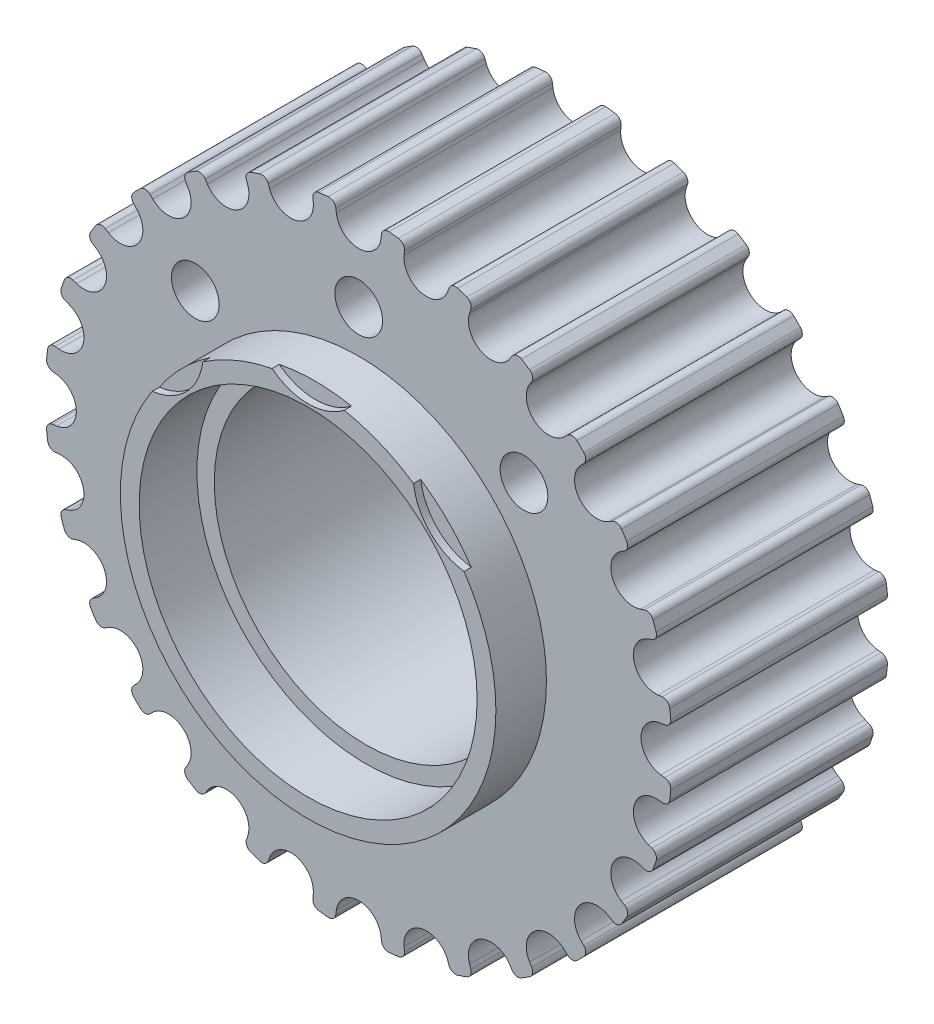
SolidWorks part; units mm, degrees
note: The reader was unsure of these and kept them because the rebuilt part matched: shared geometry of "草图15<2>".
ref_plane "前视基准面" through (0, 0, 0) normal (0, 0, 1) x (1, 0, 0)
ref_plane "上视基准面" through (0, 0, 0) normal (0, 1, 0) x (1, 0, 0)
ref_plane "右视基准面" through (0, 0, 0) normal (1, 0, 0) x (0, 0, -1)
sketch "草图2" plane through (0, 0, 0) normal (0, 0, 1) x (1, 0, 0)
  line L36 (1.3319, 20.7804) -> (1.2989, 20.5118)
  line L37 (-1.7978, 20.5118) -> (-1.8308, 20.7804)
  line L38 (-3.4222, 20.6011) -> (-3.3946, 20.3319)
  line L39 (-6.4137, 19.6428) -> (-6.5056, 19.8973)
  line L40 (-8.0172, 19.3684) -> (-7.9303, 19.1121)
  line L41 (-10.7204, 17.7684) -> (-10.8667, 17.9962)
  line L42 (-12.2227, 17.1441) -> (-12.081, 16.9135)
  line L43 (-14.5021, 14.9827) -> (-14.6954, 15.1722)
  line L44 (-15.8278, 14.0398) -> (-15.6383, 13.8465)
  line L45 (-17.5691, 11.4254) -> (-17.7997, 11.5671)
  line L46 (-18.6517, 10.2111) -> (-18.424, 10.0648)
  line L47 (-19.7676, 7.2748) -> (-20.024, 7.3616)
  line L48 (-20.5529, 5.85) -> (-20.2983, 5.7581)
  line L49 (-20.9874, 2.739) -> (-21.2567, 2.7666)
  line L50 (-21.436, 1.1752) -> (-21.1673, 1.1423)
  line L51 (-21.1673, -1.9545) -> (-21.436, -1.9875)
  line L52 (-21.2567, -3.5789) -> (-20.9874, -3.5512)
  line L53 (-20.2983, -6.5703) -> (-20.5529, -6.6623)
  line L54 (-20.024, -8.1739) -> (-19.7676, -8.087)
  line L55 (-18.424, -10.8771) -> (-18.6517, -11.0234)
  line L56 (-17.7997, -12.3793) -> (-17.5691, -12.2376)
  line L57 (-15.6383, -14.6588) -> (-15.8278, -14.8521)
  line L58 (-14.6954, -15.9845) -> (-14.5021, -15.795)
  line L59 (-12.081, -17.7258) -> (-12.2227, -17.9564)
  line L60 (-10.8667, -18.8084) -> (-10.7204, -18.5807)
  line L61 (-7.9303, -19.9243) -> (-8.0172, -20.1806)
  line L62 (-6.5056, -20.7096) -> (-6.4137, -20.455)
  line L63 (-3.3946, -21.1441) -> (-3.4222, -21.4133)
  line L64 (-1.8308, -21.5926) -> (-1.7978, -21.324)
  line L65 (1.2989, -21.324) -> (1.3319, -21.5926)
  line L66 (2.9233, -21.4133) -> (2.8957, -21.1441)
  line L67 (5.9148, -20.455) -> (6.0067, -20.7096)
  line L68 (7.5183, -20.1806) -> (7.4314, -19.9243)
  line L69 (10.2215, -18.5807) -> (10.3678, -18.8084)
  line L70 (11.7238, -17.9564) -> (11.5821, -17.7258)
  line L71 (14.0032, -15.795) -> (14.1965, -15.9845)
  line L72 (15.3289, -14.8521) -> (15.1394, -14.6588)
  line L73 (17.0702, -12.2376) -> (17.3008, -12.3793)
  line L74 (18.1528, -11.0234) -> (17.9251, -10.8771)
  line L75 (19.2687, -8.087) -> (19.5251, -8.1739)
  line L76 (20.054, -6.6623) -> (19.7994, -6.5703)
  line L77 (20.4885, -3.5512) -> (20.7578, -3.5789)
  line L78 (20.9371, -1.9875) -> (20.6684, -1.9545)
  line L79 (20.6684, 1.1423) -> (20.9371, 1.1752)
  line L80 (20.7578, 2.7666) -> (20.4885, 2.739)
  line L81 (19.7994, 5.7581) -> (20.054, 5.85)
  line L82 (19.5251, 7.3616) -> (19.2687, 7.2748)
  line L83 (17.9251, 10.0648) -> (18.1528, 10.2111)
  line L84 (17.3008, 11.5671) -> (17.0702, 11.4254)
  line L85 (15.1394, 13.8465) -> (15.3289, 14.0398)
  line L86 (14.1965, 15.1722) -> (14.0032, 14.9827)
  line L87 (11.5821, 16.9135) -> (11.7238, 17.1441)
  line L88 (10.3678, 17.9962) -> (10.2215, 17.7684)
  line L89 (7.4314, 19.1121) -> (7.5183, 19.3684)
  line L90 (6.0067, 19.8973) -> (5.9148, 19.6428)
  line L91 (2.8957, 20.3319) -> (2.9233, 20.6011)
  circle A72 centre (-0.2458, -0.3677) radius 12 construction
  circle A73 centre (-0.2458, -0.3677) radius 10.5
  arc A74 (2.9233, 20.6011) -> (2.5067, 21.1262) centre (2.4458, 20.6501) ccw
  arc A75 (2.5067, 21.1262) -> (1.8549, 21.1996) centre (-0.2495, -0.4061) ccw
  arc A76 (1.8549, 21.1996) -> (1.3319, 20.7804) centre (1.8083, 20.7219) ccw
  arc A77 (-1.7978, 20.5118) -> (1.2989, 20.5118) centre (-0.2495, 20.7019) ccw
  arc A78 (-1.8308, 20.7804) -> (-2.3538, 21.1996) centre (-2.3072, 20.7219) ccw
  arc A79 (-2.3538, 21.1996) -> (-3.0056, 21.1262) centre (-0.2495, -0.4061) ccw
  arc A80 (-3.0056, 21.1262) -> (-3.4222, 20.6011) centre (-2.9447, 20.6501) ccw
  arc A81 (-6.4137, 19.6428) -> (-3.3946, 20.3319) centre (-4.9464, 20.1727) ccw
  arc A82 (-6.5056, 19.8973) -> (-7.1087, 20.1897) centre (-6.9571, 19.7343) ccw
  arc A83 (-7.1087, 20.1897) -> (-7.7279, 19.973) centre (-0.2495, -0.4061) ccw
  arc A84 (-7.7279, 19.973) -> (-8.0172, 19.3684) centre (-7.5626, 19.5224) ccw
  arc A85 (-10.7204, 17.7684) -> (-7.9303, 19.1121) centre (-9.4079, 18.6115) ccw
  arc A86 (-10.8667, 17.9962) -> (-11.5198, 18.147) centre (-11.2706, 17.7367) ccw
  arc A87 (-11.5198, 18.147) -> (-12.0752, 17.798) centre (-0.2495, -0.4061) ccw
  arc A88 (-12.0752, 17.798) -> (-12.2227, 17.1441) centre (-11.8137, 17.3954) ccw
  arc A89 (-14.5021, 14.9827) -> (-12.081, 16.9135) centre (-13.4101, 16.0968) ccw
  arc A90 (-14.6954, 15.1722) -> (-15.3656, 15.1739) centre (-15.0314, 14.8294) ccw
  arc A91 (-15.3656, 15.1739) -> (-15.8295, 14.7101) centre (-0.2495, -0.4061) ccw
  arc A92 (-15.8295, 14.7101) -> (-15.8278, 14.0398) centre (-15.485, 14.3758) ccw
  arc A93 (-17.5691, 11.4254) -> (-15.6383, 13.8465) centre (-16.7524, 12.7545) ccw
  arc A94 (-17.7997, 11.5671) -> (-18.4535, 11.4196) centre (-18.051, 11.1582) ccw
  arc A95 (-18.4535, 11.4196) -> (-18.8026, 10.8642) centre (-0.2495, -0.4061) ccw
  arc A96 (-18.8026, 10.8642) -> (-18.6517, 10.2111) centre (-18.3923, 10.615) ccw
  arc A97 (-19.7676, 7.2748) -> (-18.424, 10.0648) centre (-19.2671, 8.7523) ccw
  arc A98 (-20.024, 7.3616) -> (-20.6286, 7.0724) centre (-20.178, 6.907) ccw
  arc A99 (-20.6286, 7.0724) -> (-20.8453, 6.4532) centre (-0.2495, -0.4061) ccw
  arc A100 (-20.8453, 6.4532) -> (-20.5529, 5.85) centre (-20.3899, 6.3015) ccw
  arc A101 (-20.9874, 2.739) -> (-20.2983, 5.7581) centre (-20.8282, 4.2909) ccw
  arc A102 (-21.2567, 2.7666) -> (-21.7818, 2.3501) centre (-21.3057, 2.2891) ccw
  arc A103 (-21.7818, 2.3501) -> (-21.8552, 1.6982) centre (-0.2495, -0.4061) ccw
  arc A104 (-21.8552, 1.6982) -> (-21.436, 1.1752) centre (-21.3775, 1.6517) ccw
  arc A105 (-21.1673, -1.9545) -> (-21.1673, 1.1423) centre (-21.3575, -0.4061) ccw
  arc A106 (-21.436, -1.9875) -> (-21.8552, -2.5104) centre (-21.3775, -2.4639) ccw
  arc A107 (-21.8552, -2.5104) -> (-21.7818, -3.1623) centre (-0.2495, -0.4061) ccw
  arc A108 (-21.7818, -3.1623) -> (-21.2567, -3.5789) centre (-21.3057, -3.1014) ccw
  arc A109 (-20.2983, -6.5703) -> (-20.9874, -3.5512) centre (-20.8282, -5.1031) ccw
  arc A110 (-20.5529, -6.6623) -> (-20.8453, -7.2654) centre (-20.3899, -7.1137) ccw
  arc A111 (-20.8453, -7.2654) -> (-20.6286, -7.8846) centre (-0.2495, -0.4061) ccw
  arc A112 (-20.6286, -7.8846) -> (-20.024, -8.1739) centre (-20.178, -7.7192) ccw
  arc A113 (-18.424, -10.8771) -> (-19.7676, -8.087) centre (-19.2671, -9.5645) ccw
  arc A114 (-18.6517, -11.0234) -> (-18.8026, -11.6764) centre (-18.3923, -11.4272) ccw
  arc A115 (-18.8026, -11.6764) -> (-18.4535, -12.2319) centre (-0.2495, -0.4061) ccw
  arc A116 (-18.4535, -12.2319) -> (-17.7997, -12.3793) centre (-18.051, -11.9704) ccw
  arc A117 (-15.6383, -14.6588) -> (-17.5691, -12.2376) centre (-16.7524, -13.5667) ccw
  arc A118 (-15.8278, -14.8521) -> (-15.8295, -15.5223) centre (-15.485, -15.1881) ccw
  arc A119 (-15.8295, -15.5223) -> (-15.3656, -15.9862) centre (-0.2495, -0.4061) ccw
  arc A120 (-15.3656, -15.9862) -> (-14.6954, -15.9845) centre (-15.0314, -15.6417) ccw
  arc A121 (-12.081, -17.7258) -> (-14.5021, -15.795) centre (-13.4101, -16.909) ccw
  arc A122 (-12.2227, -17.9564) -> (-12.0752, -18.6102) centre (-11.8137, -18.2077) ccw
  arc A123 (-12.0752, -18.6102) -> (-11.5198, -18.9592) centre (-0.2495, -0.4061) ccw
  arc A124 (-11.5198, -18.9592) -> (-10.8667, -18.8084) centre (-11.2706, -18.549) ccw
  arc A125 (-7.9303, -19.9243) -> (-10.7204, -18.5807) centre (-9.4079, -19.4238) ccw
  arc A126 (-8.0172, -20.1806) -> (-7.7279, -20.7853) centre (-7.5626, -20.3347) ccw
  arc A127 (-7.7279, -20.7853) -> (-7.1087, -21.0019) centre (-0.2495, -0.4061) ccw
  arc A128 (-7.1087, -21.0019) -> (-6.5056, -20.7096) centre (-6.9571, -20.5465) ccw
  arc A129 (-3.3946, -21.1441) -> (-6.4137, -20.455) centre (-4.9464, -20.9849) ccw
  arc A130 (-3.4222, -21.4133) -> (-3.0056, -21.9384) centre (-2.9447, -21.4623) ccw
  arc A131 (-3.0056, -21.9384) -> (-2.3538, -22.0119) centre (-0.2495, -0.4061) ccw
  arc A132 (-2.3538, -22.0119) -> (-1.8308, -21.5926) centre (-2.3072, -21.5341) ccw
  arc A133 (1.2989, -21.324) -> (-1.7978, -21.324) centre (-0.2495, -21.5141) ccw
  arc A134 (1.3319, -21.5926) -> (1.8549, -22.0119) centre (1.8083, -21.5341) ccw
  arc A135 (1.8549, -22.0119) -> (2.5067, -21.9384) centre (-0.2495, -0.4061) ccw
  arc A136 (2.5067, -21.9384) -> (2.9233, -21.4133) centre (2.4458, -21.4623) ccw
  arc A137 (5.9148, -20.455) -> (2.8957, -21.1441) centre (4.4475, -20.9849) ccw
  arc A138 (6.0067, -20.7096) -> (6.6098, -21.0019) centre (6.4582, -20.5465) ccw
  arc A139 (6.6098, -21.0019) -> (7.229, -20.7853) centre (-0.2495, -0.4061) ccw
  arc A140 (7.229, -20.7853) -> (7.5183, -20.1806) centre (7.0637, -20.3347) ccw
  arc A141 (10.2215, -18.5807) -> (7.4314, -19.9243) centre (8.909, -19.4238) ccw
  arc A142 (10.3678, -18.8084) -> (11.0209, -18.9592) centre (10.7716, -18.549) ccw
  arc A143 (11.0209, -18.9592) -> (11.5763, -18.6102) centre (-0.2495, -0.4061) ccw
  arc A144 (11.5763, -18.6102) -> (11.7238, -17.9564) centre (11.3148, -18.2077) ccw
  arc A145 (14.0032, -15.795) -> (11.5821, -17.7258) centre (12.9112, -16.909) ccw
  arc A146 (14.1965, -15.9845) -> (14.8667, -15.9862) centre (14.5325, -15.6417) ccw
  arc A147 (14.8667, -15.9862) -> (15.3306, -15.5223) centre (-0.2495, -0.4061) ccw
  arc A148 (15.3306, -15.5223) -> (15.3289, -14.8521) centre (14.9861, -15.1881) ccw
  arc A149 (17.0702, -12.2376) -> (15.1394, -14.6588) centre (16.2534, -13.5667) ccw
  arc A150 (17.3008, -12.3793) -> (17.9546, -12.2319) centre (17.5521, -11.9704) ccw
  arc A151 (17.9546, -12.2319) -> (18.3036, -11.6764) centre (-0.2495, -0.4061) ccw
  arc A152 (18.3036, -11.6764) -> (18.1528, -11.0234) centre (17.8934, -11.4272) ccw
  arc A153 (19.2687, -8.087) -> (17.9251, -10.8771) centre (18.7682, -9.5645) ccw
  arc A154 (19.5251, -8.1739) -> (20.1297, -7.8846) centre (19.6791, -7.7192) ccw
  arc A155 (20.1297, -7.8846) -> (20.3464, -7.2654) centre (-0.2495, -0.4061) ccw
  arc A156 (20.3464, -7.2654) -> (20.054, -6.6623) centre (19.891, -7.1137) ccw
  arc A157 (20.4885, -3.5512) -> (19.7994, -6.5703) centre (20.3293, -5.1031) ccw
  arc A158 (20.7578, -3.5789) -> (21.2829, -3.1623) centre (20.8067, -3.1014) ccw
  arc A159 (21.2829, -3.1623) -> (21.3563, -2.5104) centre (-0.2495, -0.4061) ccw
  arc A160 (21.3563, -2.5104) -> (20.9371, -1.9875) centre (20.8786, -2.4639) ccw
  arc A161 (20.6684, 1.1423) -> (20.6684, -1.9545) centre (20.8585, -0.4061) ccw
  arc A162 (20.9371, 1.1752) -> (21.3563, 1.6982) centre (20.8786, 1.6517) ccw
  arc A163 (21.3563, 1.6982) -> (21.2829, 2.3501) centre (-0.2495, -0.4061) ccw
  arc A164 (21.2829, 2.3501) -> (20.7578, 2.7666) centre (20.8067, 2.2891) ccw
  arc A165 (19.7994, 5.7581) -> (20.4885, 2.739) centre (20.3293, 4.2909) ccw
  arc A166 (20.054, 5.85) -> (20.3464, 6.4532) centre (19.891, 6.3015) ccw
  arc A167 (20.3464, 6.4532) -> (20.1297, 7.0724) centre (-0.2495, -0.4061) ccw
  arc A168 (20.1297, 7.0724) -> (19.5251, 7.3616) centre (19.6791, 6.907) ccw
  arc A169 (17.9251, 10.0648) -> (19.2687, 7.2748) centre (18.7682, 8.7523) ccw
  arc A170 (18.1528, 10.2111) -> (18.3036, 10.8642) centre (17.8934, 10.615) ccw
  arc A171 (18.3036, 10.8642) -> (17.9546, 11.4196) centre (-0.2495, -0.4061) ccw
  arc A172 (17.9546, 11.4196) -> (17.3008, 11.5671) centre (17.5521, 11.1582) ccw
  arc A173 (15.1394, 13.8465) -> (17.0702, 11.4254) centre (16.2534, 12.7545) ccw
  arc A174 (15.3289, 14.0398) -> (15.3306, 14.7101) centre (14.9861, 14.3758) ccw
  arc A175 (15.3306, 14.7101) -> (14.8667, 15.1739) centre (-0.2495, -0.4061) ccw
  arc A176 (14.8667, 15.1739) -> (14.1965, 15.1722) centre (14.5325, 14.8294) ccw
  arc A177 (11.5821, 16.9135) -> (14.0032, 14.9827) centre (12.9112, 16.0968) ccw
  arc A178 (11.7238, 17.1441) -> (11.5763, 17.798) centre (11.3148, 17.3954) ccw
  arc A179 (11.5763, 17.798) -> (11.0209, 18.147) centre (-0.2495, -0.4061) ccw
  arc A180 (11.0209, 18.147) -> (10.3678, 17.9962) centre (10.7716, 17.7367) ccw
  arc A181 (7.4314, 19.1121) -> (10.2215, 17.7684) centre (8.909, 18.6115) ccw
  arc A182 (7.5183, 19.3684) -> (7.229, 19.973) centre (7.0637, 19.5224) ccw
  arc A183 (7.229, 19.973) -> (6.6098, 20.1897) centre (-0.2495, -0.4061) ccw
  arc A184 (6.6098, 20.1897) -> (6.0067, 19.8973) centre (6.4582, 19.7343) ccw
  arc A185 (2.8957, 20.3319) -> (5.9148, 19.6428) centre (4.4475, 20.1727) ccw
extrude "凸台-拉伸1" add sketch "草图2" along normal blind 15
move or copy body "实体-移动/复制1" bodies to move or copy 106 copy no translate (-21.7751, 0, 0)
sketch "草图12" plane through (0, 0, 15) normal (0, 0, 1) x (1, 0, 0)
  circle A0 centre (-22.0209, -0.3677) radius 10.5 construction
  circle A1 centre (-22.0209, -0.3677) radius 10.5
  circle A2 centre (-22.0246, -0.3096) radius 11.7
  circle A3 centre (-22.0246, -0.3096) radius 13
  circle A4 centre (-22.0209, -0.3677) radius 16
  point P7 (-6.0209, -0.3677)
  point P10 (-10.7072, -11.6815)
  point P11 (-22.0209, -16.3677)
  point P12 (-33.3346, -11.6815)
  point P13 (-38.0209, -0.3677)
  point P14 (-33.3346, 10.946)
  point P15 (-22.0209, 15.6323)
  point P16 (-10.7072, 10.946)
  point P17 (-22.0209, -0.3677)
  dimension "D1" = 23.4
  dimension "D2" = 26
  dimension "D3" = 32
  dimension "D4" = 8
extrude "凸台-拉伸2" add sketch "草图12" along normal blind 3.5 and the other way blind 19.5 contours A3 A2
hole_wizard "M4 螺纹孔1" positions "3D草图1" profile "草图13" tap size "M4" standard "GB" end condition through all
sketch3d "3D草图1"
  circle A0 centre (-22.0209, -0.3677, 15) radius 16 construction
  point P0 (-33.3346, 10.946, 15)
  point P3 (-22.0209, 15.6323, 15)
  point P6 (-10.5793, 10.8166, 15)
  point P10 (-22.0209, -0.3677, 31)
cosmetic thread "孔螺蚊线4" parameters "D2"=4
cosmetic thread "孔螺蚊线5" parameters "D2"=4
cosmetic thread "孔螺蚊线6" parameters "D2"=4
sketch "草图13" plane through (-33.3346, 10.946, 15) normal (1, 0, 0) x (0, -1, 0)
  line L0 (0, 0) -> (0, 19.5)
  line L1 (0, 19.5) -> (1.65, 19.5)
  line L2 (1.65, 19.5) -> (1.65, 0)
  line L5 (1.65, 0) -> (0, 0)
  line L11 (0, -6.35) -> (0, 107.95) construction
  dimension "通孔螺纹孔钻头直径" = 3.3
  dimension "通孔螺纹孔钻头深度" = 19.5
sketch "草图14" plane through (0, 0, 15) normal (0, 0, 1) x (1, 0, 0)
  circle A0 centre (-22.0209, -0.3677) radius 10.5 construction
  circle A1 centre (-22.0246, -0.3096) radius 11.7
  circle A2 centre (-22.0246, -0.3096) radius 11.7
  circle A3 centre (-22.0209, -0.3677) radius 10.5
  dimension "D1" = 0
extrude "切除-拉伸1" cut sketch "草图14" against normal blind 0.5
sketch "草图15" plane through (0, 0, 15) normal (0, 0, 1) x (1, 0, 0)
  circle A0 centre (-22.0209, -0.3677) radius 16 construction
  circle A1 centre (-22.0209, -0.3677) radius 16 construction
  circle A2 centre (-22.0209, 15.6323) radius 4.05
  circle A3 centre (-10.7072, 10.946) radius 4.05
  circle A4 centre (-6.0209, -0.3677) radius 4.05 [skipped]
  circle A8 centre (-38.0209, -0.3677) radius 4.05 [skipped]
  circle A9 centre (-33.3346, 10.946) radius 4.05
  circle A10 centre (-10.7072, -11.6815) radius 4.05 [skipped]
  circle A11 centre (-33.3346, -11.6815) radius 4.05 [skipped]
  circle A12 centre (-22.0209, -16.3677) radius 4.05 [skipped]
  point P0 (-33.3346, -11.6815)
  point P2 (-22.0209, -16.3677)
  point P4 (-10.7072, -11.6815)
  point P6 (-10.7072, 10.946)
  point P8 (-22.0209, 15.6323)
  point P10 (-33.3346, 10.946)
  point P34 (-22.0209, -0.3677)
  dimension "D1" = 8.1
  dimension "D2" = 8
extrude "切除-拉伸2" cut sketch "草图15" against normal blind 0.5 from surface at 3.5 starting at face at (-10.3246, -0.3096, 18.5)
extrude "切除-拉伸3" cut sketch "草图15<2>" along normal blind 1.5 from surface at -19.5
sketch "草图15<2>" plane through (0, 0, 15) normal (0, 0, 1) x (1, 0, 0) same geometry as "草图15"
sketch "草图16" plane through (0, 0, 0) normal (0, 0, -1) x (-1, 0, 0)
  circle A0 centre (22.0209, -0.3677) radius 10.5 construction
  circle A1 centre (22.0246, -0.3096) radius 11.7
  circle A2 centre (22.0246, -0.3096) radius 11.7
  circle A3 centre (22.0209, -0.3677) radius 10.5
  dimension "D1" = 0
extrude "凸台-拉伸3" add sketch "草图16" along normal blind 0.5
